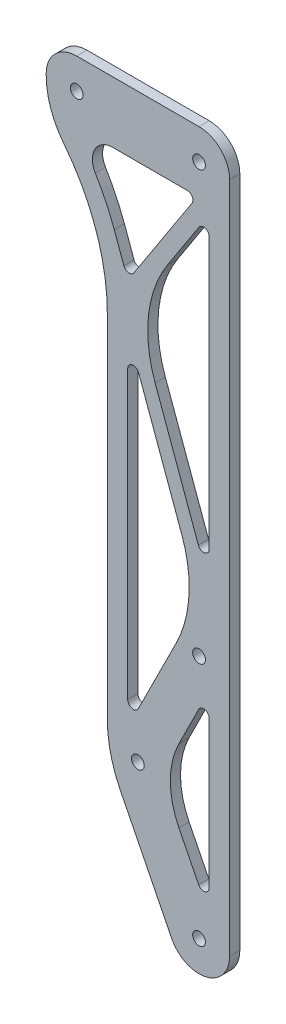
SolidWorks part; units mm, degrees
material "7075-T6, Plate (SS)"
ref_plane "Front Plane" through (0, 0, 0) normal (0, 0, 1) x (1, 0, 0)
ref_plane "Top Plane" through (0, 0, 0) normal (0, 1, 0) x (1, 0, 0)
ref_plane "Right Plane" through (0, 0, 0) normal (1, 0, 0) x (0, 0, -1)
sketch "Sketch1" plane through (0, 0, 0) normal (0, 0, 1) x (1, 0, 0)
  line L0 (19.05, 254) -> (19.05, 0) construction
  line L1 (0, 0) -> (76.2, 0) construction
  line L2 (0, 0) -> (0, 254) construction
  line L3 (0, 254) -> (76.2, 254) construction
  line L4 (76.2, 0) -> (76.2, 254) construction
  line L5 (57.15, 254) -> (57.15, 0) construction
  line L6 (-19.05, 438.15) -> (57.15, 438.15) construction
  line L7 (-76.2, 457.2) -> (76.2, 457.2) construction
  line L8 (-76.2, 457.2) -> (-76.2, 419.1) construction
  line L9 (-76.2, 419.1) -> (76.2, 419.1) construction
  line L10 (76.2, 457.2) -> (76.2, 419.1) construction
  line L11 (38.1, 495.3) -> (76.2, 495.3) construction
  line L12 (38.1, 495.3) -> (38.1, 457.2) construction
  line L13 (38.1, 457.2) -> (76.2, 457.2) construction
  line L14 (76.2, 495.3) -> (76.2, 457.2) construction
  line L15 (-38.1, 457.2) -> (-38.1, 419.1)
  line L16 (-38.1, 419.1) -> (0, 373.6942)
  line L17 (0, 373.6942) -> (0, 0)
  line L18 (0, 0) -> (76.2, 0)
  line L19 (76.2, 0) -> (76.2, 457.2)
  line L20 (76.2, 457.2) -> (-38.1, 457.2)
  line L21 (57.15, 19.05) -> (19.05, 95.25)
  line L22 (19.05, 95.25) -> (57.15, 171.45)
  point P12 (0, -2.6634)
  point P14 (76.2, 438.15)
  dimension "D1" = 254
  dimension "D2" = 76.2
  dimension "D3" = 19.05
  dimension "D4" = 19.05
  dimension "D5" = 38.1
  dimension "D6" = 152.4
  dimension "D7" = 76.2
  dimension "D8" = 19.05
  dimension "D9" = 76.2
  dimension "D10" = 457.2
  dimension "D11" = 19.05
  dimension "D12" = 19.05
  dimension "D13" = 50
extrude "Boss-Extrude1" add sketch "Sketch1" along normal blind 6.35 contours L19 L20 L15 L16 L17 L18 region at (34.6846, 240.8694, 0)
hole_wizard "5/16 (0.3125) Diameter Hole1" positions "Sketch3" profile "Sketch4" hole size "5/16" standard "ANSI Inch" end condition through all
sketch "Sketch3" plane through (0, 0, 6.35) normal (0, 0, 1) x (1, 0, 0)
  point P0 (-19.05, 438.15)
  point P3 (57.15, 438.15)
  point P6 (57.15, 171.45)
  point P9 (19.05, 95.25)
  point P12 (57.15, 19.05)
sketch "Sketch4" plane through (-19.05, 438.15, 6.35) normal (1, 0, 0) x (0, -1, 0)
  line L0 (0, 0) -> (0, 6.35)
  line L1 (0, 6.35) -> (3.9687, 6.35)
  line L2 (3.9687, 6.35) -> (3.9687, 0)
  line L5 (3.9687, 0) -> (0, 0)
  line L11 (0, -6.35) -> (0, 107.95) construction
  dimension "Thru Hole Dia." = 7.9375
  dimension "Thru Hole Depth" = 6.35
fillet "Fillet2" radius 127 1 edges at (0, 373.6942, 3.175)
sketch "Sketch7" plane through (0, 0, 6.35) normal (0, 0, 1) x (1, 0, 0)
  line L0 (12.7, 110.9481) -> (12.7, 327.47)
  line L1 (56.2675, 419.1) -> (12.7, 352.1053)
  line L2 (63.5, 212.5481) -> (63.5, 419.1)
  line L3 (76.2, 0) -> (76.2, 457.2) construction
  line L4 (63.5, 419.1) -> (-21.5485, 419.1)
  line L5 (12.7, 110.9481) -> (63.5, 212.5481)
  line L6 (57.6341, 200.8162) -> (12.7, 324.2586)
  line L7 (63.5, 212.5481) -> (4.2734, 375.2546)
  line L8 (0, 0) -> (45.3765, 0)
  line L9 (0, 0) -> (76.2, 0) construction
  line L10 (45.3765, 0) -> (0, 90.7529)
  line L11 (0, 327.47) -> (0, 0) construction
  line L12 (0, 90.7529) -> (0, 0)
  line L13 (63.5, 155.7519) -> (33.249, 95.25)
  line L14 (33.249, 95.25) -> (63.5, 34.7481)
  line L15 (63.5, 34.7481) -> (63.5, 155.7519)
  line L16 (63.5, 412.75) -> (16.7775, 340.9037)
  circle A1 centre (57.15, 438.15) radius 3.9687 construction
  arc A2 (12.7, 327.47) -> (-19.9836, 417.2674) centre (-127, 327.47) ccw
  arc A3 (12.7, 327.47) -> (-21.5485, 419.1) centre (-127, 327.47) ccw
  circle A4 centre (57.15, 171.45) radius 3.9687 construction
  circle A5 centre (19.05, 95.25) radius 3.9687 construction
  circle A6 centre (57.15, 19.05) radius 3.9687 construction
  line M23 (0, 327.47) -> (0, 0)
  line M24 (0, 0) -> (76.2, 0)
  dimension "D1" = 19.05
  dimension "D5" = 12.7
  dimension "D7" = 19.05
  dimension "D10" = 12.7
  dimension "D2" = 12.7
  dimension "D4" = 12.7
  dimension "D6" = 9.525
  dimension "D8" = 19.05
  dimension "D9" = 12.7
  dimension "D11" = 12.7
  dimension "D12" = 9.525
  dimension "D13" = 6.35
  dimension "D3" = 12.7
extrude "Cut-Extrude4" cut sketch "Sketch7" against normal through all contours A3 L7 L1 L4 | L2 L16 L7 | L5 L6 L0 | L10 M24 M23 | L14 L15 L13 region at (27.678, 212.0076, 6.35) region at (47.9258, 322.0673, 6.35) region at (17.4038, 397.4307, 6.35) region at (15.1255, 30.251, 6.35) region at (53.4163, 95.25, 6.35)
fillet "Fillet8" radius 76.2 3 edges at (0, 90.7529, 3.175) (16.7775, 340.9037, 3.175) (57.6341, 200.8162, 3.175)
fillet "Fillet9" radius 19.05 2 edges at (76.2, 457.2, 3.175) (-38.1, 457.2, 3.175)
fillet "Fillet11" 2 edges at (45.3765, 0, 3.175) (76.2, 0, 3.175) type full round first side face at (26.7106, 37.3318, 3.175) second side face at (76.2, 219.075, 3.175) middle face at (60.7882, 0, 3.175)
fillet "Fillet12" radius 50.8 2 edges at (-38.1, 419.1, 3.175) (33.249, 95.25, 3.175)
fillet "Fillet13" radius 3.4925 8 edges at (12.7, 352.1053, 3.175) (12.7, 324.2586, 3.175) (63.5, 412.75, 3.175) (63.5, 155.7519, 3.175) (12.7, 110.9481, 3.175) (63.5, 34.7481, 3.175) (63.5, 212.5481, 3.175) (56.2675, 419.1, 3.175)
fillet "Fillet15" radius 12.7 1 edges at (-21.5485, 419.1, 3.175)
